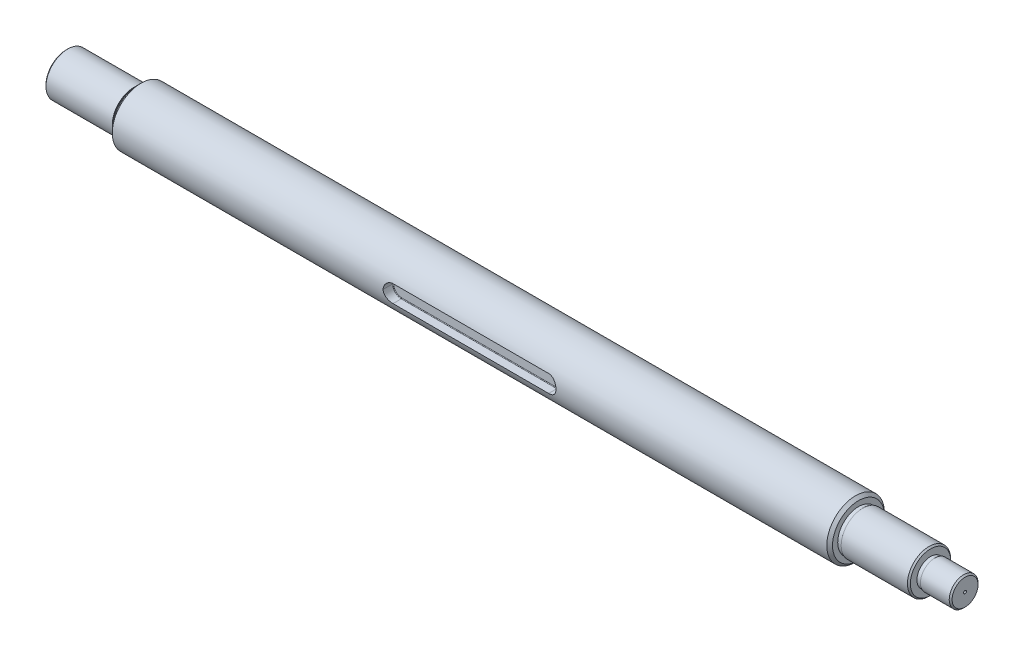
SolidWorks part; units mm, degrees
ref_plane "Front Plane" through (0, 0, 0) normal (0, 0, 1) x (1, 0, 0)
ref_plane "Top Plane" through (0, 0, 0) normal (0, 1, 0) x (1, 0, 0)
ref_plane "Right Plane" through (0, 0, 0) normal (1, 0, 0) x (0, 0, -1)
sketch "Sketch1" plane through (0, 0, 0) normal (0, 0, 1) x (1, 0, 0)
  line L0 (0, 0) -> (312, 0) construction
  line L1 (0, 0) -> (0, 7.5)
  line L2 (0, 7.5) -> (25, 7.5)
  line L3 (25, 7.5) -> (25, 9)
  line L4 (26, 10) -> (274, 10)
  line L5 (275, 9) -> (275, 7.5)
  line L6 (275, 7.5) -> (300, 7.5)
  line L7 (300, 7.5) -> (300, 5)
  line L8 (300, 5) -> (312, 5)
  line L9 (312, 5) -> (312, 0)
  line L10 (312, 0) -> (0, 0)
  line L11 (26, 10) -> (25, 9)
  line L12 (274, 10) -> (275, 9)
  dimension "L" = 312
  dimension "P" = 15
  dimension "D" = 20
  dimension "Q" = 10
  dimension "LA" = 25
  dimension "L_s_1" = 250
  dimension "LB" = 25
  dimension "LC" = 12
  dimension "D1" = 45
  dimension "D3" = 45
  dimension "Ds" = 18
revolve "Revolve1" add sketch "Sketch1" angle 360 about L0
cosmetic thread "Cosmetic Thread1" [suppressed] parameters "MA"=5, "TD_s"=6.619
cosmetic thread "Cosmetic Thread2" [suppressed] parameters "MSA"=5, "TD_s"=6.619
cosmetic thread "Cosmetic Thread3" [suppressed] parameters "MMA"=5, "TD_s"=6.619
cosmetic thread "Cosmetic Thread4" [suppressed] parameters "MB"=5, "TD_s"=6.619
cosmetic thread "Cosmetic Thread5" [suppressed] parameters "MSB"=5, "TD_s"=6.619
cosmetic thread "Cosmetic Thread6" [suppressed] parameters "MMB"=5, "TD_s"=6.619
cosmetic thread "Cosmetic Thread7" [suppressed] parameters "MC"=5, "TD_s"=4.891
cosmetic thread "Cosmetic Thread8" [suppressed] parameters "MSC"=5, "TD_s"=4.891
cosmetic thread "Cosmetic Thread9" [suppressed] parameters "MMC"=5, "TD_s"=4.891
chamfer "Chamfer1" distance 0.5 angle 45 3 edges at (312, 0, 5) (300, 0, 7.5) (0, 0, 7.5)
sketch "Sketch2" plane through (0, 0, 0) normal (0, 0, 1) x (1, 0, 0)
  line L0 (0, 0) -> (312, 0) construction
  line L1 (312, -4.5) -> (312, 4.5) construction
  line L2 (0, 0) -> (0, 0.5)
  line L3 (0, 7) -> (0, -7) construction
  line L4 (0, 0.5) -> (0.5, 0)
  line L5 (0.5, 0) -> (0, 0)
  line L6 (312, 0) -> (312, 0.5)
  line L7 (312, 0.5) -> (311.5, 0)
  line L8 (311.5, 0) -> (312, 0)
  dimension "D1" = 1
  dimension "D2" = 0.5
revolve "Cut-Revolve1" cut sketch "Sketch2" angle 360 about L0
sketch "Sketch3" plane through (0, 0, 0) normal (0, 0, 1) x (1, 0, 0)
  line L0 (0, 0) -> (312, 0) construction
  line L1 (312, -4.5) -> (312, 4.5) construction
  line L3 (23.5, 7.5) -> (25, 7.5)
  line L4 (23.5, 7.5) -> (23.5, 7.2)
  line L5 (23.5, 7.2) -> (25, 7.2)
  line L6 (25, 7.5) -> (25, 7.2)
  line L7 (25, 7.5) -> (25, 9) construction
  line L8 (0, 7.5) -> (25, 7.5) construction
  line L9 (275, 9) -> (275, 7.5) construction
  line L10 (275, 7.5) -> (276.5, 7.5)
  line L11 (275, 7.5) -> (275, 7.2)
  line L12 (275, 7.2) -> (276.5, 7.2)
  line L13 (276.5, 7.5) -> (276.5, 7.2)
  line L14 (275, 7.5) -> (300, 7.5) construction
  line L15 (300, 5) -> (301.5, 5)
  line L16 (300, 5) -> (300, 4.7)
  line L17 (300, 4.7) -> (301.5, 4.7)
  line L18 (301.5, 5) -> (301.5, 4.7)
  line L19 (300, 7.5) -> (300, 5) construction
  line L20 (300, 5) -> (312, 5) construction
  dimension "D1" = 1.5
  dimension "D2" = 0.3
revolve "Cut-Revolve2" cut sketch "Sketch3" angle 360 about L0
ref_plane "Plane1" through (0, 0, 10) normal (0, 0, 1) x (1, 0, 0)
ref_plane "Plane2" through (0, 0, 7.5) normal (0, 0, 1) x (1, 0, 0)
ref_plane "Plane3" through (0, 0, 5) normal (0, 0, 1) x (1, 0, 0)
ref_plane "Plane4" through (25, 0, 0) normal (1, 0, 0) x (0, 0, -1)
ref_plane "Plane5" through (275, 0, 0) normal (1, 0, 0) x (0, 0, -1)
ref_plane "Plane6" through (312, 0, 0) normal (1, 0, 0) x (0, 0, -1)
other "DeleteFace1" [suppressed]
other "DeleteFace2" [suppressed]
other "DeleteFace3" [suppressed]
other "DeleteFace4" [suppressed]
other "DeleteFace5" [suppressed]
other "DeleteFace6" [suppressed]
other "DeleteFace7" [suppressed]
other "DeleteFace8" [suppressed]
other "DeleteFace9" [suppressed]
hole_wizard "Tapped Hole1" [suppressed] positions "Sketch5" profile "Sketch4" tap size "M3x0.5" standard "JIS"
sketch "Sketch5" [suppressed] plane through (0, 0, 0) normal (-1, 0, 0) x (0, 0, 1)
  point P0 (0, 0)
sketch "Sketch4" [suppressed] plane through (0, 0, 0) normal (0, 1, 0) x (0, 0, 1)
  line L0 (0, 0) -> (0, 9.2511)
  line L1 (0, 9.2511) -> (1.25, 8.5)
  line L2 (1.25, 8.5) -> (1.25, 0)
  line L5 (1.25, 0) -> (0, 0)
  line L10 (0, 9.2511) -> (-1.25, 8.5) construction
  line L11 (0, 0) -> (0, 9.2511) construction
  dimension "Tap Drill Dia." = 2.5
  dimension "Tap Drill Depth" = 8.5
  dimension "Drill Angle" = 118
cosmetic thread "Hole Thread1" [suppressed] parameters "NAx2"=6, "NA"=3
hole_wizard "Tapped Hole2" [suppressed] positions "Sketch7" profile "Sketch6" tap size "M3x0.5" standard "JIS"
sketch "Sketch7" [suppressed] plane through (50, 0, 0) normal (1, 0, 0) x (0, 0, -1)
  point P0 (0, 0)
sketch "Sketch6" [suppressed] plane through (50, 0, 0) normal (0, 1, 0) x (0, 0, -1)
  line L0 (0, 0) -> (0, 9.2511)
  line L1 (0, 9.2511) -> (1.25, 8.5)
  line L2 (1.25, 8.5) -> (1.25, 0)
  line L5 (1.25, 0) -> (0, 0)
  line L10 (0, 9.2511) -> (-1.25, 8.5) construction
  line L11 (0, 0) -> (0, 9.2511) construction
  dimension "Tap Drill Dia." = 2.5
  dimension "Tap Drill Depth" = 8.5
  dimension "Drill Angle" = 118
cosmetic thread "Hole Thread2" [suppressed] parameters "NCx2"=6, "NC"=3
ref_plane "Dim. KA" [suppressed] through (2, 0, 0) normal (1, 0, 0) x (0, 0, -1)
sketch "Sketch8" [suppressed] plane through (0, 0, 4) normal (0, 0, 1) x (1, 0, 0)
  line L0 (2, 0) -> (6, 0) construction
  line L1 (2, 1.5) -> (6, 1.5)
  line L2 (2, 1.5) -> (2, -1.5)
  line L3 (2, -1.5) -> (6, -1.5)
  line L4 (6, 1.5) -> (6, -1.5)
  line L5 (2, -5.5) -> (2, 5.5) construction
  dimension "B_s_1" = 3
  dimension "HA_1" = 4
extrude "Cut-Extrude1" [suppressed] cut sketch "Sketch8" against normal blind 1.8
fillet "Fillet1" [suppressed] radius 1.5
fillet "Fillet2" [suppressed] radius 1.5
fillet "Fillet3" [suppressed] radius 0.1
ref_plane "Dim. KB" through (120, 0, 0) normal (1, 0, 0) x (0, 0, -1)
sketch "Sketch9" plane through (0, 0, 10) normal (0, 0, 1) x (1, 0, 0)
  line L0 (120, 0) -> (180, 0) construction
  line L1 (120, 3) -> (180, 3)
  line L2 (120, 3) -> (120, -3)
  line L3 (120, -3) -> (180, -3)
  line L4 (180, 3) -> (180, -3)
  line L5 (120, -5.5) -> (120, 5.5) construction
  dimension "B_s_2" = 6
  dimension "HB_1" = 60
extrude "Cut-Extrude2" cut sketch "Sketch9" against normal blind 3.5
fillet "Fillet4" radius 3 2 edges at (120, 3, 8.0197) (120, -3, 8.0197)
fillet "Fillet5" radius 3 2 edges at (180, 3, 8.0197) (180, -3, 8.0197)
fillet "Fillet6" radius 0.2 6 edges at (150, 3, 6.5) (120.8787, 2.1213, 6.5) (150, -3, 6.5) (120.8787, -2.1213, 6.5) (179.1213, 2.1213, 6.5) (179.1213, -2.1213, 6.5)
ref_plane "Dim. KC" [suppressed] through (48, 0, 0) normal (1, 0, 0) x (0, 0, -1)
sketch "Sketch10" [suppressed] plane through (0, 0, 3) normal (0, 0, 1) x (1, 0, 0)
  line L0 (44, 0) -> (48, 0) construction
  line L1 (44, 1) -> (48, 1)
  line L2 (44, 1) -> (44, -1)
  line L3 (44, -1) -> (48, -1)
  line L4 (48, 1) -> (48, -1)
  line L5 (48, -5.5) -> (48, 5.5) construction
  dimension "B_s_3" = 2
  dimension "HC_1" = 4
extrude "Cut-Extrude3" [suppressed] cut sketch "Sketch10" against normal blind 1.2
fillet "Fillet7" [suppressed] radius 1
fillet "Fillet8" [suppressed] radius 1
fillet "Fillet9" [suppressed] radius 0.1
sketch "Sketch11" [suppressed] plane through (0, 0, 10) normal (0, 0, 1) x (1, 0, 0)
  line L0 (162, 0) -> (182, 0) construction
  line L1 (162, 3) -> (182, 3)
  line L2 (162, 3) -> (162, -3)
  line L3 (162, -3) -> (182, -3)
  line L4 (182, 3) -> (182, -3)
  line L5 (12, 7.5) -> (12, 9) construction
  dimension "B_s_2" = 6
  dimension "HD_1" = 20
  dimension "KD" = 150
extrude "Cut-Extrude4" [suppressed] cut sketch "Sketch11" against normal blind 3.5
fillet "Fillet10" [suppressed] radius 3
fillet "Fillet11" [suppressed] radius 3
fillet "Fillet12" [suppressed] radius 0.2
ref_plane "Dim. ZA" [suppressed] through (2, 0, 0) normal (1, 0, 0) x (0, 0, -1)
ref_plane "Dim. AA_1" [suppressed] through (0, 0, 0) normal (0, -1, 0) x (1, 0, 0)
sketch "Sketch12" [suppressed] plane through (0, 0, 4) normal (0, 0, 1) x (1, 0, 0)
  line L0 (2, 0) -> (6, 0) construction
  line L1 (2, 1.5) -> (6, 1.5)
  line L2 (2, 1.5) -> (2, -1.5)
  line L3 (2, -1.5) -> (6, -1.5)
  line L4 (6, 1.5) -> (6, -1.5)
  line L5 (2, -5.5) -> (2, 5.5) construction
  dimension "B_s_1" = 3
  dimension "HA_2" = 4
extrude "Cut-Extrude5" [suppressed] cut sketch "Sketch12" against normal blind 1.8
fillet "Fillet13" [suppressed] radius 1.5
fillet "Fillet14" [suppressed] radius 1.5
fillet "Fillet15" [suppressed] radius 0.1
sketch "Sketch13" [suppressed] plane through (0, 0, 0) normal (0, -1, 0) x (1, 0, 0)
  line L0 (0, 0) -> (6, 0) construction
  line L1 (2, -3) -> (6, -3)
  line L2 (2, -3) -> (2, -4)
  line L3 (2, -4) -> (6, -4)
  line L4 (6, -3) -> (6, -4)
  line L6 (2, -5.5) -> (2, 5.5) construction
  line L7 (2, 4) -> (6, 4) construction
  dimension "H_1" = 1
  dimension "P" = 15
extrude "Cut-Extrude6" [suppressed] cut sketch "Sketch13" against normal through all and the other way through all
ref_plane "Dim. ZB" [suppressed] through (14, 0, 0) normal (1, 0, 0) x (0, 0, -1)
ref_plane "Dim. AB_1" [suppressed] through (0, 0, 0) normal (0, -1, 0) x (1, 0, 0)
sketch "Sketch14" [suppressed] plane through (0, 0, 5) normal (0, 0, 1) x (1, 0, 0)
  line L0 (14, 0) -> (18, 0) construction
  line L1 (14, 1.5) -> (18, 1.5)
  line L2 (14, 1.5) -> (14, -1.5)
  line L3 (14, -1.5) -> (18, -1.5)
  line L4 (18, 1.5) -> (18, -1.5)
  line L5 (14, -5.5) -> (14, 5.5) construction
  dimension "B_s_2" = 6
  dimension "HB_2" = 4
extrude "Cut-Extrude7" [suppressed] cut sketch "Sketch14" against normal blind 3.5
fillet "Fillet16" [suppressed] radius 3
fillet "Fillet17" [suppressed] radius 3
fillet "Fillet18" [suppressed] radius 0.2
sketch "Sketch15" [suppressed] plane through (0, 0, 0) normal (0, -1, 0) x (1, 0, 0)
  line L0 (0, 0) -> (18, 0) construction
  line L3 (14, -5.5) -> (14, 5.5) construction
  line L4 (14, -4) -> (18, -4)
  line L5 (14, -4) -> (14, -5)
  line L6 (14, -5) -> (18, -5)
  line L7 (18, -4) -> (18, -5)
  line L8 (14, 5) -> (18, 5) construction
  dimension "H_2" = 1
  dimension "D" = 20
extrude "Cut-Extrude8" [suppressed] cut sketch "Sketch15" against normal through all and the other way through all
ref_plane "Dim. ZC" [suppressed] through (48, 0, 0) normal (1, 0, 0) x (0, 0, -1)
ref_plane "Dim. AC_1" [suppressed] through (0, 0, 0) normal (0, -1, 0) x (1, 0, 0)
sketch "Sketch16" [suppressed] plane through (0, 0, 3) normal (0, 0, 1) x (1, 0, 0)
  line L0 (44, 0) -> (48, 0) construction
  line L2 (44, 1) -> (48, 1)
  line L3 (44, 1) -> (44, -1)
  line L4 (44, -1) -> (48, -1)
  line L5 (48, 1) -> (48, -1)
  line L6 (48, -5.5) -> (48, 5.5) construction
  dimension "B_s_3" = 2
  dimension "HC_2" = 4
extrude "Cut-Extrude9" [suppressed] cut sketch "Sketch16" against normal blind 1.2
fillet "Fillet19" [suppressed] radius 1
fillet "Fillet20" [suppressed] radius 1
fillet "Fillet21" [suppressed] radius 0.1
sketch "Sketch17" [suppressed] plane through (0, 0, 0) normal (0, -1, 0) x (1, 0, 0)
  line L0 (0, 0) -> (48, 0) construction
  line L1 (48, -5.5) -> (48, 5.5) construction
  line L2 (44, -2.5) -> (48, -2.5)
  line L3 (44, -2.5) -> (44, -3.5)
  line L4 (44, -3.5) -> (48, -3.5)
  line L5 (48, -2.5) -> (48, -3.5)
  line L6 (44, 3) -> (48, 3) construction
  dimension "H_3" = 1
  dimension "Q" = 10
extrude "Cut-Extrude10" [suppressed] cut sketch "Sketch17" against normal through all and the other way through all
ref_plane "Dim. ZD" [suppressed] through (20, 0, 0) normal (1, 0, 0) x (0, 0, -1)
ref_plane "Dim. AD_1" [suppressed] through (0, 0, 0) normal (0, -1, 0) x (1, 0, 0)
sketch "Sketch18" [suppressed] plane through (0, 0, 5) normal (0, 0, 1) x (1, 0, 0)
  line L0 (20, 0) -> (24, 0) construction
  line L1 (20, 1.5) -> (24, 1.5)
  line L2 (20, 1.5) -> (20, -1.5)
  line L3 (20, -1.5) -> (24, -1.5)
  line L4 (24, 1.5) -> (24, -1.5)
  line L5 (20, -5.5) -> (20, 5.5) construction
  dimension "B_s_2" = 6
  dimension "HD_2" = 4
extrude "Cut-Extrude11" [suppressed] cut sketch "Sketch18" against normal blind 3.5
fillet "Fillet22" [suppressed] radius 3
fillet "Fillet23" [suppressed] radius 3
fillet "Fillet24" [suppressed] radius 0.2
sketch "Sketch19" [suppressed] plane through (0, 0, 0) normal (0, -1, 0) x (1, 0, 0)
  line L0 (20, -5.5) -> (20, 5.5) construction
  line L1 (20, -4) -> (24, -4)
  line L2 (20, -4) -> (20, -5)
  line L3 (20, -5) -> (24, -5)
  line L4 (24, -4) -> (24, -5)
  line L5 (24, 0) -> (0, 0) construction
  line L7 (20, 5) -> (24, 5) construction
  dimension "H_2" = 1
  dimension "D" = 20
extrude "Cut-Extrude12" [suppressed] cut sketch "Sketch19" against normal through all and the other way through all
sketch "Sketch20" [suppressed] plane through (0, 0, 0) normal (0, 0, 1) x (1, 0, 0)
  line L0 (0, 0) -> (50, 0) construction
  line L2 (50, 3) -> (50, 0) construction
  line L3 (3.1, 4) -> (4, 4)
  line L4 (3.1, 4) -> (3.1, 3.5)
  line L5 (3.1, 3.5) -> (4, 3.5)
  line L6 (4, 4) -> (4, 3.5)
  line L7 (0, 4) -> (12, 4) construction
  line L8 (0, 0) -> (0, 4) construction
  dimension "M_s_1" = 0.9
  dimension "D_s_1" = 7
  dimension "TA" = 4
revolve "Cut-Revolve3" [suppressed] cut sketch "Sketch20" angle 360 about L0
sketch "Sketch21" [suppressed] plane through (0, 0, 0) normal (0, 0, 1) x (1, 0, 0)
  line L0 (38, 4) -> (38, 3) construction
  line L1 (34, 4) -> (34.9, 4)
  line L2 (34, 4) -> (34, 3.5)
  line L3 (34, 3.5) -> (34.9, 3.5)
  line L4 (34.9, 4) -> (34.9, 3.5)
  line L5 (50, 0) -> (0, 0) construction
  line L7 (26, 4) -> (38, 4) construction
  line L8 (50, 3) -> (50, 0) construction
  dimension "TB" = 4
  dimension "M_s_1" = 0.9
  dimension "D_s_1" = 7
revolve "Cut-Revolve4" [suppressed] cut sketch "Sketch21" angle 360 about L5
sketch "Sketch22" [suppressed] plane through (0, 0, 0) normal (0, 0, 1) x (1, 0, 0)
  line L0 (0, 0) -> (50, 0) construction
  line L1 (50, 3) -> (50, 0) construction
  line L2 (46, 3) -> (46.7, 3)
  line L3 (46, 3) -> (46, 2.5)
  line L4 (46, 2.5) -> (46.7, 2.5)
  line L5 (46.7, 3) -> (46.7, 2.5)
  line L6 (38, 3) -> (50, 3) construction
  dimension "TC" = 4
  dimension "M_s_2" = 0.7
  dimension "D_s_2" = 5
revolve "Cut-Revolve5" [suppressed] cut sketch "Sketch22" angle 360 about L0
sketch "Sketch23" [suppressed] plane through (0, 0, 0) normal (0, 1, 0) x (1, 0, 0)
  line L0 (0, 0) -> (50, 0) construction
  line L2 (50, 0) -> (0, 0) construction
  line L3 (2, 4) -> (10, 4)
  line L4 (2, 4) -> (2, 3.5)
  line L5 (2, 3.5) -> (10, 3.5)
  line L6 (10, 4) -> (10, 3.5)
  line L7 (2, -3.5) -> (10, -3.5)
  line L8 (2, -3.5) -> (2, -4)
  line L9 (2, -4) -> (10, -4)
  line L10 (10, -3.5) -> (10, -4)
  line L12 (-8.2094, -4) -> (8.2094, -4) construction
  dimension "W1_1" = 7
  dimension "SA" = 2
  dimension "L_s_2" = 8
extrude "Cut-Extrude13" [suppressed] cut sketch "Sketch23" against normal through all and the other way through all
sketch "Sketch24" [suppressed] plane through (0, 0, 0) normal (0, 1, 0) x (1, 0, 0)
  line L0 (0, 0) -> (50, 0) construction
  line L2 (12, 5) -> (12, -5) construction
  line L3 (14, 5) -> (22, 5)
  line L4 (14, 5) -> (14, 4)
  line L5 (14, 4) -> (22, 4)
  line L6 (22, 5) -> (22, 4)
  line L7 (14, -4) -> (22, -4)
  line L8 (14, -4) -> (14, -5)
  line L9 (14, -5) -> (22, -5)
  line L10 (22, -4) -> (22, -5)
  line L11 (-6.3285, -5) -> (6.3285, -5) construction
  dimension "SD" = 2
  dimension "L_s_3" = 8
  dimension "W" = 8
extrude "Cut-Extrude14" [suppressed] cut sketch "Sketch24" against normal through all and the other way through all
sketch "Sketch25" [suppressed] plane through (0, 0, 0) normal (0, 1, 0) x (1, 0, 0)
  line L0 (0, 0) -> (50, 0) construction
  line L3 (-5.5, -3) -> (5.5, -3) construction
  line L4 (40, 3) -> (48, 3)
  line L5 (40, 3) -> (40, 2.75)
  line L6 (40, 2.75) -> (48, 2.75)
  line L7 (48, 3) -> (48, 2.75)
  line L8 (40, -2.75) -> (48, -2.75)
  line L9 (40, -2.75) -> (40, -3)
  line L10 (40, -3) -> (48, -3)
  line L11 (48, -2.75) -> (48, -3)
  dimension "SC" = 2
  dimension "L_s_4" = 8
  dimension "W1_2" = 5.5
extrude "Cut-Extrude15" [suppressed] cut sketch "Sketch25" along normal through all and the other way through all
ref_plane "Dim. WA" [suppressed] through (2, 0, 0) normal (1, 0, 0) x (0, 0, -1)
ref_plane "Dim. GA" [suppressed] through (6, 0, 0) normal (1, 0, 0) x (0, 0, -1)
sketch "Sketch26" [suppressed] plane through (2, 0, 0) normal (1, 0, 0) x (0, 0, -1)
  line L0 (-3, 2.6458) -> (-3, -2.6458)
  line L1 (-4, 0) -> (4, 0) construction
  circle A0 centre (0, 0) radius 4 construction
  arc A1 (-3, 2.6458) -> (-3, -2.6458) centre (0, 0) ccw
  dimension "H_1" = 1
extrude "Cut-Extrude16" [suppressed] cut sketch "Sketch26" along normal up to surface (4 mm away)
sketch "Sketch27" [suppressed] plane through (2, 0, 0) normal (1, 0, 0) x (0, 0, -1)
  line L0 (4, 0) -> (-4, 0) construction
  line L1 (0, -4) -> (0, 4) construction
  line L2 (0, 0) -> (0, -4) construction
  line L3 (-2.6458, -3) -> (2.6458, -3)
  arc A0 (-2.6458, -3) -> (2.6458, -3) centre (0, 0) ccw
  dimension "AA_2" = 90
  dimension "H_1" = 1
extrude "Cut-Extrude17" [suppressed] cut sketch "Sketch27" along normal up to surface (4 mm away)
ref_plane "Dim. WD" [suppressed] through (14, 0, 0) normal (1, 0, 0) x (0, 0, -1)
ref_plane "Dim. GD" [suppressed] through (18, 0, 0) normal (1, 0, 0) x (0, 0, -1)
sketch "Sketch28" [suppressed] plane through (14, 0, 0) normal (1, 0, 0) x (0, 0, -1)
  line L0 (-4, 3) -> (-4, -3)
  line L1 (-5, 0) -> (5, 0) construction
  circle A0 centre (0, 0) radius 5 construction
  arc A1 (-4, 3) -> (-4, -3) centre (0, 0) ccw
  dimension "H_2" = 1
extrude "Cut-Extrude18" [suppressed] cut sketch "Sketch28" along normal up to surface (4 mm away)
sketch "Sketch29" [suppressed] plane through (14, 0, 0) normal (1, 0, 0) x (0, 0, -1)
  line L0 (5, 0) -> (0, 0) construction
  line L1 (0, -5) -> (0, 5) construction
  line L2 (0, 0) -> (0, -5) construction
  line L3 (-3, -4) -> (3, -4)
  arc A0 (-3, -4) -> (3, -4) centre (0, 0) ccw
  dimension "AC_2" = 90
  dimension "H_2" = 1
extrude "Cut-Extrude19" [suppressed] cut sketch "Sketch29" along normal up to surface (4 mm away)
ref_plane "Dim. WC" [suppressed] through (48, 0, 0) normal (1, 0, 0) x (0, 0, -1)
ref_plane "Dim. GC" [suppressed] through (44, 0, 0) normal (1, 0, 0) x (0, 0, -1)
sketch "Sketch30" [suppressed] plane through (48, 0, 0) normal (1, 0, 0) x (0, 0, -1)
  line L0 (-2, 2.2361) -> (-2, -2.2361)
  line L1 (-3, 0) -> (3, 0) construction
  circle A0 centre (0, 0) radius 3 construction
  arc A1 (-2, 2.2361) -> (-2, -2.2361) centre (0, 0) ccw
  dimension "H_3" = 1
extrude "Cut-Extrude20" [suppressed] cut sketch "Sketch30" against normal up to surface (4 mm away)
sketch "Sketch31" [suppressed] plane through (48, 0, 0) normal (1, 0, 0) x (0, 0, -1)
  line L0 (-3, 0) -> (3, 0) construction
  line L1 (0, 3) -> (0, -3) construction
  line L2 (0, 0) -> (0, -3) construction
  line L3 (-2.2361, -2) -> (2.2361, -2)
  arc A0 (-2.2361, -2) -> (2.2361, -2) centre (0, 0) ccw
  dimension "AB_2" = 90
  dimension "H_3" = 1
extrude "Cut-Extrude21" [suppressed] cut sketch "Sketch31" against normal up to surface (4 mm away)
ref_plane "Dim. WE_1" [suppressed] through (14, 0, 0) normal (1, 0, 0) x (0, 0, -1)
ref_plane "Dim. WE_2" [suppressed] through (24, 0, 0) normal (1, 0, 0) x (0, 0, -1)
ref_plane "Dim. GE_1" [suppressed] through (18, 0, 0) normal (1, 0, 0) x (0, 0, -1)
ref_plane "Dim. GE_2" [suppressed] through (20, 0, 0) normal (1, 0, 0) x (0, 0, -1)
sketch "Sketch32" [suppressed] plane through (14, 0, 0) normal (1, 0, 0) x (0, 0, -1)
  line L0 (-4, 3) -> (-4, -3)
  line L1 (-5, 0) -> (5, 0) construction
  circle A0 centre (0, 0) radius 5 construction
  arc A1 (-4, 3) -> (-4, -3) centre (0, 0) ccw
  dimension "H_2" = 1
extrude "Cut-Extrude22" [suppressed] cut sketch "Sketch32" along normal up to surface (4 mm away)
sketch "Sketch33" [suppressed] plane through (24, 0, 0) normal (1, 0, 0) x (0, 0, -1)
  line L0 (-4, 3) -> (-4, -3)
  line L1 (-5, 0) -> (5, 0) construction
  circle A0 centre (0, 0) radius 5 construction
  arc A1 (-4, 3) -> (-4, -3) centre (0, 0) ccw
  dimension "H_2" = 1
extrude "Cut-Extrude23" [suppressed] cut sketch "Sketch33" against normal up to surface (4 mm away)
sketch "Sketch34" [suppressed] plane through (14, 0, 0) normal (1, 0, 0) x (0, 0, -1)
  line L0 (-5, 0) -> (5, 0) construction
  line L1 (0, 5) -> (0, -5) construction
  line L2 (0, 0) -> (0, -5) construction
  line L3 (-3, -4) -> (3, -4)
  arc A0 (-3, -4) -> (3, -4) centre (0, 0) ccw
  dimension "AD_2" = 90
  dimension "H_2" = 1
extrude "Cut-Extrude24" [suppressed] cut sketch "Sketch34" along normal up to surface (4 mm away)
sketch "Sketch35" [suppressed] plane through (24, 0, 0) normal (1, 0, 0) x (0, 0, -1)
  line L0 (-5, 0) -> (5, 0) construction
  line L1 (0, 5) -> (0, -5) construction
  line L2 (0, 0) -> (0, -5) construction
  line L3 (-3, -4) -> (3, -4)
  arc A0 (-3, -4) -> (3, -4) centre (0, 0) ccw
  dimension "AD_2" = 90
  dimension "H_2" = 1
extrude "Cut-Extrude25" [suppressed] cut sketch "Sketch35" against normal up to surface (4 mm away)
equation "\"Plane dim_1\"= \"D@Sketch1\" * 0.5"
equation "\"Plane dim_2\"= \"P@Sketch1\" * 0.5"
equation "\"Plane dim_3\"= \"Q@Sketch1\" * 0.5"
equation "\"D1@Fillet1\"= \"B_s_1@Sketch8\" * 0.5"
equation "\"D1@Fillet2\" = \"B_s_1@Sketch8\" * 0.5"
equation "\"D1@Fillet4\"= \"B_s_2@Sketch9\" * 0.5"
equation "\"D1@Fillet5\" = \"B_s_2@Sketch9\" * 0.5"
equation "\"D1@Fillet7\"= \"B_s_3@Sketch10\" * 0.5"
equation "\"D1@Fillet8\" = \"B_s_3@Sketch10\" * 0.5"
equation "\"D1@Fillet13\"= \"B_s_1@Sketch12\" * 0.5"
equation "\"D1@Fillet14\" = \"B_s_1@Sketch12\" * 0.5"
equation "\"D1@Fillet16\"= \"B_s_2@Sketch14\" * 0.5"
equation "\"D1@Fillet17\" = \"B_s_2@Sketch14\" * 0.5"
equation "\"D1@Fillet10\"= \"B_s_2@Sketch11\" * 0.5"
equation "\"D1@Fillet11\" = \"B_s_2@Sketch11\" * 0.5"
equation "\"D1@Fillet19\"  = \"B_s_3@Sketch16\" * 0.5"
equation "\"D1@Fillet20\" = \"B_s_3@Sketch16\" * 0.5"
equation "\"D1@Fillet22\"= \"B_s_2@Sketch18\" * 0.5"
equation "\"D1@Fillet23\" = \"B_s_2@Sketch18\" * 0.5"
